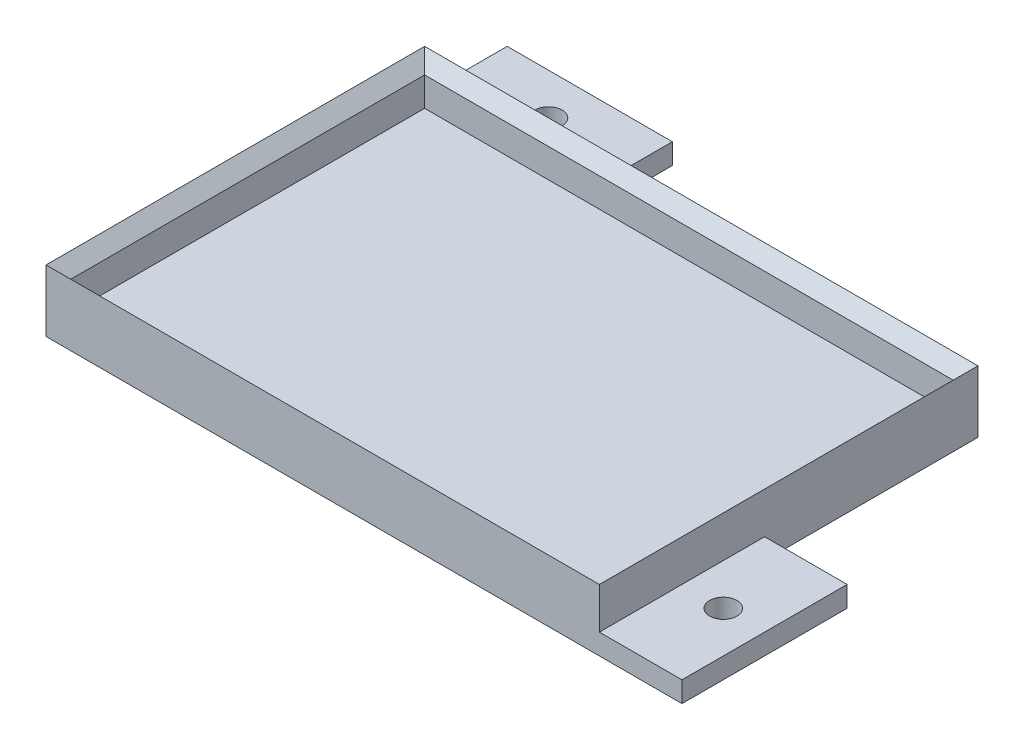
SolidWorks part; units mm, degrees
ref_plane "Front Plane" through (0, 0, 0) normal (0, 0, 1) x (1, 0, 0)
ref_plane "Top Plane" through (0, 0, 0) normal (0, 1, 0) x (1, 0, 0)
ref_plane "Right Plane" through (0, 0, 0) normal (1, 0, 0) x (0, 0, -1)
sketch "Sketch1" plane through (0, 0, 0) normal (0, 1, 0) x (1, 0, 0)
  line L1 (-67, 45.84) -> (67, 45.84)
  line L2 (-67, 45.84) -> (-67, -45.84)
  line L3 (-67, -45.84) -> (67, -45.84)
  line L4 (67, 45.84) -> (67, -45.84)
  point P4 (0, 45.84)
  point P6 (-67, 0)
  dimension "D1" = 134
  dimension "D2" = 91.68
extrude "Boss-Extrude1" add sketch "Sketch1" along normal blind 5
sketch "Sketch2" plane through (0, 0, 0) normal (0, 1, 0) x (1, 0, 0)
  line L1 (-67, 45.84) -> (-27, 45.84)
  line L2 (-67, 45.84) -> (-67, 65.84)
  line L3 (-67, 65.84) -> (-27, 65.84)
  line L4 (-27, 45.84) -> (-27, 65.84)
  line L5 (67, -45.84) -> (87, -45.84)
  line L6 (67, -45.84) -> (67, -5.84)
  line L7 (67, -5.84) -> (87, -5.84)
  line L8 (87, -45.84) -> (87, -5.84)
  dimension "D1" = 40
  dimension "D2" = 40
  dimension "D3" = 20
  dimension "D4" = 20
extrude "Boss-Extrude2" add sketch "Sketch2" along normal blind 5
sketch "Sketch5" plane through (0, 5, 0) normal (0, 1, 0) x (1, 0, 0)
  line L1 (-47, 55.84) -> (-47, 65.84) construction
  line L2 (-27, 65.84) -> (-67, 65.84) construction
  line L4 (87, -25.84) -> (77, -25.84) construction
  line L5 (87, -45.84) -> (87, -5.84) construction
  point P0 (-47, 55.84)
  point P2 (77, -25.84)
  dimension "D1" = 10
  dimension "D2" = 10
hole_wizard "M6 Clearance Hole1" positions "Sketch5" profile "Sketch4" hole size "M6" standard "ISO" end condition through all
sketch "Sketch4" plane through (-47, 5, -55.84) normal (1, 0, 0) x (0, 0, 1)
  line L0 (0, 0) -> (0, 5)
  line L1 (0, 5) -> (3.3, 5)
  line L2 (3.3, 5) -> (3.3, 0)
  line L5 (3.3, 0) -> (0, 0)
  line L11 (0, -6.35) -> (0, 107.95) construction
  dimension "Thru Hole Dia." = 6.6
  dimension "Thru Hole Depth" = 5
sketch "Sketch6" plane through (0, 5, 0) normal (0, 1, 0) x (1, 0, 0)
  line L1 (67, 45.84) -> (-67, 45.84)
  line L2 (67, 45.84) -> (67, -45.84)
  line L3 (67, -45.84) -> (-67, -45.84)
  line L4 (-67, 45.84) -> (-67, -45.84)
  line L5 (-64, 42.84) -> (64, 42.84)
  line L6 (-64, 42.84) -> (-64, -42.84)
  line L7 (-64, -42.84) -> (64, -42.84)
  line L8 (64, 42.84) -> (64, -42.84)
  point P10 (0, 42.84)
  point P12 (-64, 0)
  dimension "D1" = 3
  dimension "D2" = 3
extrude "Boss-Extrude3" add sketch "Sketch6" along normal blind 10
chamfer "Chamfer1" distance 3 angle 45 4 edges at (-64, 15, 0) (0, 15, 42.84) (64, 15, 0) (0, 15, -42.84)
equation "\"D2@Sketch1\"=85.48 + 2 * 3 + 0.2"
equation "\"D1@Sketch1\"=127.8 + 2 * 3 + 0.2"
